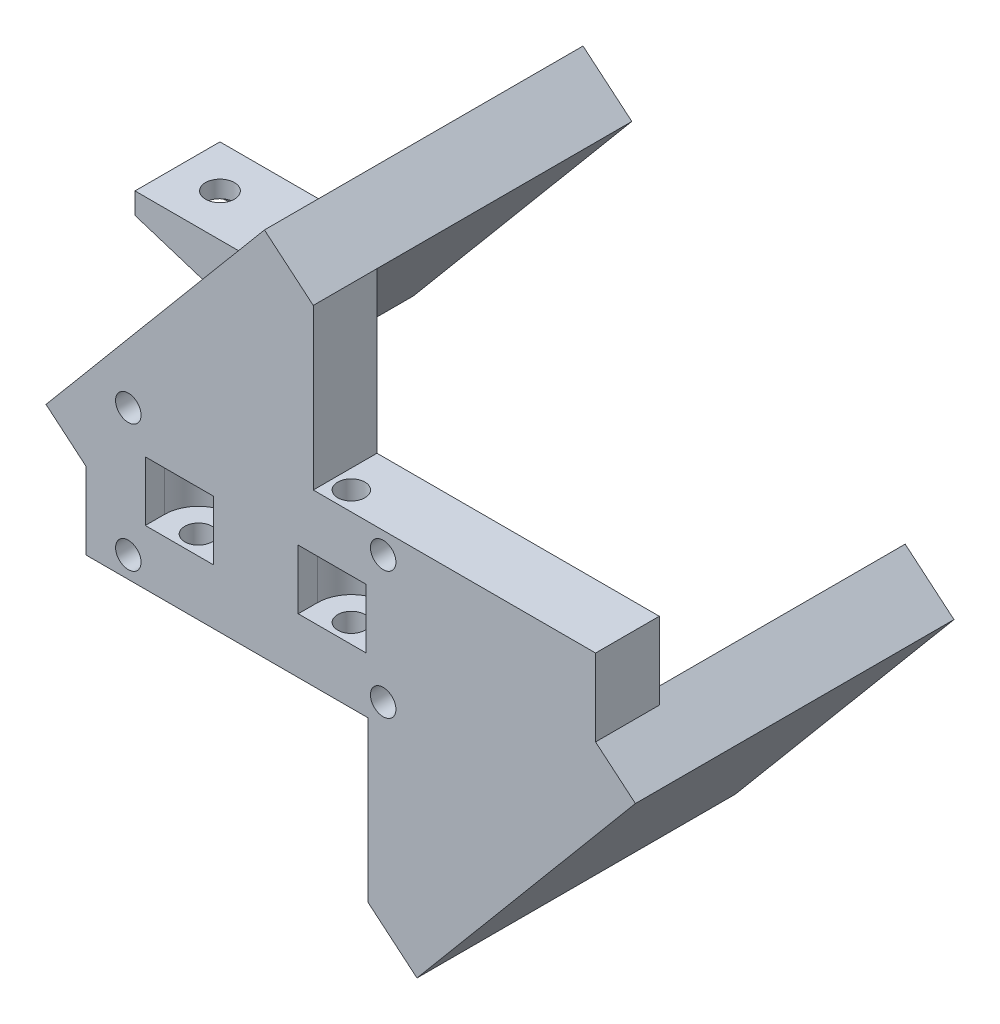
SolidWorks part; units mm, degrees
ref_plane "Front Plane" through (0, 0, 0) normal (0, 0, 1) x (1, 0, 0)
ref_plane "Top Plane" through (0, 0, 0) normal (0, 1, 0) x (1, 0, 0)
ref_plane "Right Plane" through (0, 0, 0) normal (1, 0, 0) x (0, 0, -1)
sketch "Sketch1" plane through (0, 0, 0) normal (0, 0, 1) x (1, 0, 0)
  line L2 (0, 0) -> (0, 23.1549)
  line L3 (2.2451, 25.4) -> (76.2, 25.4)
  line L10 (76.2, 2.2451) -> (76.2, 25.4)
  line L11 (0, 0) -> (73.9549, 0)
  line L12 (0, 23.1549) -> (2.2451, 25.4)
  line L13 (76.2, 2.2451) -> (73.9549, 0)
  dimension "D1" = 76.2
  dimension "D2" = 25.4
  dimension "D3" = 3.175
  dimension "D4" = 3.175
  dimension "D5" = 135
  dimension "D6" = 135
extrude "Boss-Extrude1" add sketch "Sketch1" along normal blind 9.525
ref_plane "Plane1" through (0, 12.7, 0) normal (0, 1, 0) x (1, 0, 0)
ref_plane "Plane2" through (25.4, 0, 0) normal (1, 0, 0) x (0, 0, -1)
sketch "Sketch2" plane through (0, 0, 9.525) normal (0, 0, 1) x (1, 0, 0)
  line L0 (0, 0) -> (73.9549, 0) construction
  line L1 (0, 23.1549) -> (0, 0) construction
  circle A0 centre (6.35, 22.225) radius 1.905
  dimension "D1" = 3.81
  dimension "D2" = 22.225
  dimension "D3" = 6.35
extrude "Cut-Extrude1" cut sketch "Sketch2" against normal through all
sketch "Sketch4" plane through (0, 12.7, 0) normal (0, 1, 0) x (1, 0, 0)
  line L7 (76.2, -9.525) -> (2.2451, -9.525) construction
  line L8 (8.89, -6.6675) -> (8.89, -9.525)
  line L9 (19.05, -6.6675) -> (19.05, -9.525)
  line L10 (19.05, -9.525) -> (8.89, -9.525)
  line L11 (0, -9.525) -> (0, 0) construction
  arc A2 (19.05, -6.6675) -> (8.89, -6.6675) centre (13.97, -6.6675) ccw
  dimension "D1" = 10.16
  dimension "D2" = 2.8575
  dimension "D3" = 13.97
extrude "Cut-Extrude2" cut sketch "Sketch4" against normal mid plane 8.89
sketch "Sketch5" plane through (0, 25.4, 0) normal (0, 1, 0) x (1, 0, 0)
  line L0 (76.2, -9.525) -> (2.2451, -9.525) construction
  line L1 (0, -9.525) -> (0, 0) construction
  circle A0 centre (13.97, -6.6675) radius 2.032
  dimension "D3" = 4.064
  dimension "D1" = 2.8575
  dimension "D2" = 13.97
extrude "Cut-Extrude3" cut sketch "Sketch5" against normal blind 28.575
sketch "Sketch13" plane through (0, 0, 0) normal (-1, 0, 0) x (0, 0, 1)
  line L0 (9.525, 25.4) -> (0, 25.4) construction
  line L1 (4.7625, 12.7) -> (0, 12.7) construction
  line L4 (4.7625, 12.7) -> (9.525, 12.7) construction
  circle A0 centre (4.7625, 12.7) radius 1.905
  dimension "D1" = 3.81
  dimension "D2" = 12.7
extrude "Cut-Extrude8" cut sketch "Sketch13" against normal blind 6.35
mirror "Mirror1" about plane through (0, 12.7, 0) normal (0, 1, 0) of "Cut-Extrude1"
mirror "Mirror2" about plane through (25.4, 0, 0) normal (1, 0, 0) of "Cut-Extrude3", "Cut-Extrude2", "Mirror1"
sketch "Sketch22" plane through (0, 0, 0) normal (0, 0, -1) x (-1, 0, 0)
  line L0 (-33.9964, 49.3007) -> (-1.3428, 10.3856)
  line L1 (-1.3428, 10.3856) -> (5.9538, 16.5082)
  line L2 (5.9538, 16.5082) -> (-26.6998, 55.4232)
  line L3 (-26.6998, 55.4232) -> (-33.9964, 49.3007)
  line L4 (0, 0) -> (-73.9549, 0) construction
  line L5 (-26.6998, 55.4232) -> (-1.3428, 10.3856) construction
  line L9 (-82.1538, 8.8918) -> (-49.5002, -30.0232)
  line L10 (-49.5002, -30.0232) -> (-42.2036, -23.9007)
  line L11 (-42.2036, -23.9007) -> (-74.8572, 15.0144)
  line L12 (-74.8572, 15.0144) -> (-82.1538, 8.8918)
  line L13 (-74.8572, 15.0144) -> (-49.5002, -30.0232) construction
  line L16 (-74.8572, 15.0144) -> (-74.8572, 25.4) construction
  line L17 (-76.2, 25.4) -> (-2.2451, 25.4) construction
  line L18 (-1.3428, 10.3856) -> (-1.3428, 0) construction
  line L19 (-74.8572, 20.2072) -> (-76.2, 20.2072) construction
  line L20 (-76.2, 2.2451) -> (-76.2, 25.4) construction
  line L21 (-1.3428, 5.1928) -> (0, 5.1928) construction
  line L22 (0, 23.1549) -> (0, 0) construction
  dimension "D1" = 50
  dimension "D2" = 9.525
  dimension "D3" = 9.525
  dimension "D4" = 50.8
  dimension "D5" = 53.34
  dimension "D6" = 50.8
extrude "Boss-Extrude5" add sketch "Sketch22" along normal blind 38.1
sketch "Sketch23" plane through (0, 0, 9.525) normal (0, 0, 1) x (1, 0, 0)
  line L17 (0, 11.5124) -> (-5.9538, 16.5082)
  line L20 (26.6998, 55.4232) -> (33.9964, 49.3007)
  line L21 (33.9964, 49.3007) -> (33.9964, 25.4)
  line L22 (76.2, 25.4) -> (2.2451, 25.4) construction
  line L26 (76.2, 13.8876) -> (82.1538, 8.8918)
  line L29 (49.5002, -30.0232) -> (42.2036, -23.9007)
  line L30 (42.2036, -23.9007) -> (42.2036, 0)
  line L31 (0, 0) -> (73.9549, 0) construction
  line L33 (0, 11.5124) -> (0, 22.2158)
  line L34 (0, 23.1549) -> (0, 0) construction
  line L35 (0, 22.2158) -> (2.4825, 25.4)
  line L36 (2.4825, 25.4) -> (33.9964, 25.4)
  line L37 (-5.9538, 16.5082) -> (26.6998, 55.4232)
  line L38 (42.2036, 0) -> (62.2586, 0)
  line L39 (62.2586, 0) -> (76.2, 13.8876)
  line L40 (82.1538, 8.8918) -> (49.5002, -30.0232)
extrude "Boss-Extrude6" add sketch "Sketch23" against normal up to surface (9.525 mm away) up to face at (10.1327, 29.5285, 0)
ref_plane "Plane3" through (0, 0, -19.05) normal (0, 0, -1) x (-1, 0, 0)
sketch "Sketch24" plane through (0, 0, -19.05) normal (0, 0, -1) x (-1, 0, 0)
  line L4 (1.9511, 21.2784) -> (-4.1715, 28.575)
  line L5 (5.9538, 16.5082) -> (-26.6998, 55.4232) construction
  line L6 (5.9538, 16.5082) -> (-26.6998, 55.4232) construction
  line L7 (-4.1715, 28.575) -> (14.8785, 28.575)
  line L9 (1.9511, 21.2784) -> (14.8785, 25.4)
  line L10 (14.8785, 25.4) -> (14.8785, 28.575)
  dimension "D1" = 50
  dimension "D2" = 19.05
  dimension "D3" = 9.525
  dimension "D4" = 28.575
  dimension "D5" = 3.175
extrude "Boss-Extrude7" add sketch "Sketch24" along normal mid plane 12.7
sketch "Sketch26" plane through (0, 28.575, 0) normal (0, 1, 0) x (1, 0, 0)
  line L1 (-14.8785, 25.4) -> (-14.8785, 12.7) construction
  line L2 (-14.8785, 12.7) -> (4.1715, 12.7) construction
  circle A0 centre (-8.5285, 19.05) radius 2.159
  dimension "D1" = 4.318
  dimension "D2" = 6.35
  dimension "D3" = 6.35
extrude "Cut-Extrude9" cut sketch "Sketch26" against normal blind 6.35
ref_plane "Plane4" through (0, 26.035, 0) normal (0, 1, 0) x (1, 0, 0)
sketch "Sketch27" plane through (0, 26.035, 0) normal (0, 1, 0) x (1, 0, 0)
  line L0 (-14.8785, 25.4) -> (-14.8785, 12.7) construction
  line L1 (-4.0835, 21.6163) -> (-8.5285, 24.1826)
  line L2 (-8.5285, 24.1826) -> (-12.9735, 21.6163)
  line L3 (-12.9735, 21.6163) -> (-12.9735, 16.4837)
  line L4 (-12.9735, 16.4837) -> (-8.5285, 13.9174)
  line L5 (-8.5285, 13.9174) -> (-4.0835, 16.4837)
  line L6 (-4.0835, 16.4837) -> (-4.0835, 21.6163)
  circle A0 centre (-8.5285, 19.05) radius 4.445 construction
  circle A1 centre (-8.5285, 19.05) radius 2.159 construction
  point P12 (-11.6414, 16.4837)
  dimension "D1" = 8.89
extrude "Cut-Extrude10" cut sketch "Sketch27" against normal up to surface (2.6595 mm away) up to face at (-10.6875, 24.0638, -19.05)
